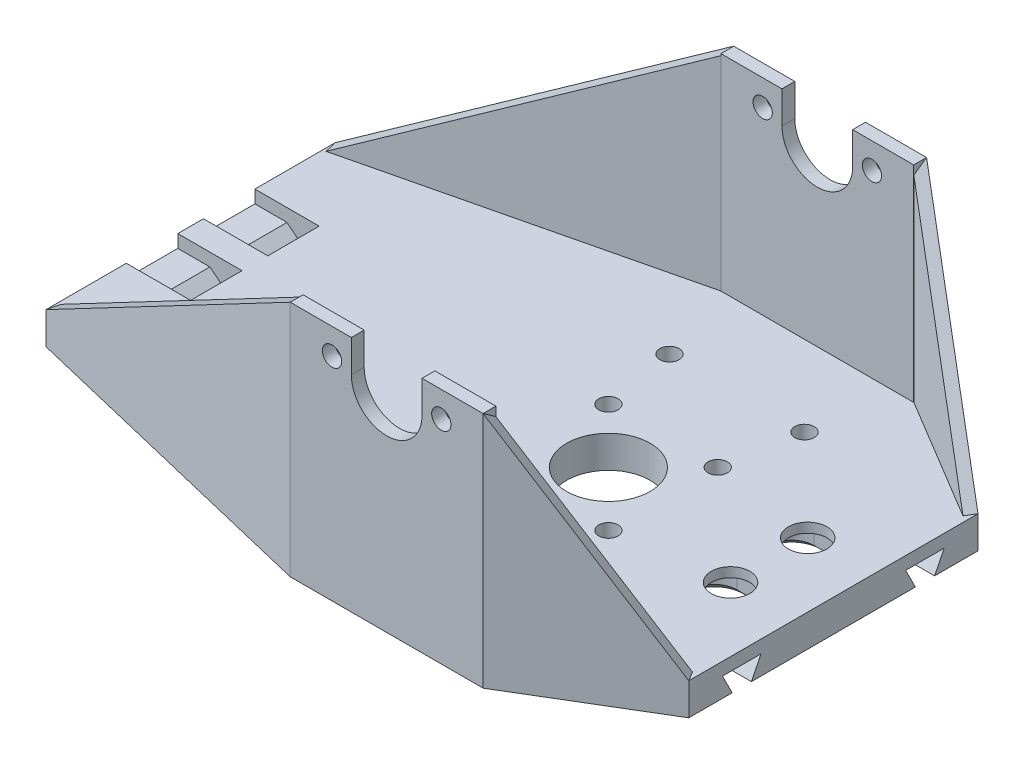
SolidWorks part; units mm, degrees
ref_plane "Front Plane" through (0, 0, 0) normal (0, 0, 1) x (1, 0, 0)
ref_plane "Top Plane" through (0, 0, 0) normal (0, 1, 0) x (1, 0, 0)
ref_plane "Right Plane" through (0, 0, 0) normal (1, 0, 0) x (0, 0, -1)
sketch "Sketch1" plane through (0, 0, 0) normal (0, 1, 0) x (1, 0, 0)
  line L1 (-15, 32.5) -> (15, 32.5)
  line L2 (-15, 32.5) -> (-15, -32.5)
  line L3 (-15, -32.5) -> (15, -32.5)
  line L4 (15, 32.5) -> (15, -32.5)
  point P4 (0, 32.5)
  point P6 (15, 0)
  dimension "D1" = 30
  dimension "D2" = 65
extrude "Boss-Extrude1" add sketch "Sketch1" along normal blind 2
sketch "Sketch5" plane through (0, 0, 32.5) normal (0, 0, 1) x (1, 0, 0)
  line L1 (-15, 0) -> (15, 0)
  line L2 (-15, 0) -> (-15, 34)
  line L3 (-15, 34) -> (15, 34)
  line L4 (15, 0) -> (15, 34)
  line L5 (-8.5, 0) -> (8.5, 0) construction
  line L6 (-8.5, 0) -> (-8.5, 30) construction
  line L7 (-8.5, 30) -> (8.5, 30) construction
  line L8 (8.5, 0) -> (8.5, 30) construction
  line L9 (-5.5, 34) -> (5.5, 34)
  line L10 (-5.5, 34) -> (-5.5, 29)
  line L11 (-5.5, 29) -> (5.5, 29) construction
  line L12 (5.5, 34) -> (5.5, 29)
  circle A0 centre (-8.5, 30) radius 1.5
  circle A1 centre (8.5, 30) radius 1.5
  arc A2 (-5.5, 29) -> (5.5, 29) centre (0, 29) ccw
  point P5 (0, 30)
  point P11 (0, 34)
  point P18 (0, 29)
  line M14 (-15, 0) -> (15, 0)
  line M15 (15, 0) -> (15, 2)
  line M16 (15, 2) -> (-15, 2)
  line M17 (-15, 2) -> (-15, 0)
  dimension "D4" = 3
  dimension "D5" = 3
  dimension "D1" = 34
  dimension "D2" = 30
  dimension "D3" = 17
  dimension "D6" = 11
  dimension "D7" = 5
extrude "Boss-Extrude2" add sketch "Sketch5" along normal blind 2 contours A2 L10 L3 L2 L4 L12 A1 A0 M16 | M17 M14 M15 M16 region at (0, 1, 32.5) region at (0, 16.4302, 32.5)
mirror "Mirror1" about plane through (0, 0, 0) normal (0, 0, 1) of "Boss-Extrude2"
sketch "Sketch6" plane through (0, 2, 0) normal (0, 1, 0) x (1, 0, 0)
  line L0 (15, -32.5) -> (15, 32.5) construction
  line L1 (-65, 22.5) -> (35, 22.5) construction
  line L2 (-65, 22.5) -> (-65, -22.5)
  line L3 (-65, -22.5) -> (35, -22.5) construction
  line L4 (35, 22.5) -> (35, -22.5)
  line L5 (-65, 22.5) -> (-15, 34.5)
  line L6 (-15, 34.5) -> (15, 34.5)
  line L7 (15, 34.5) -> (35, 22.5)
  line L8 (35, -22.5) -> (15, -34.5)
  line L9 (15, -34.5) -> (-15, -34.5)
  line L10 (-15, -34.5) -> (-65, -22.5)
  point P4 (35, 0)
  dimension "D1" = 45
  dimension "D2" = 100
  dimension "D3" = 20
extrude "Boss-Extrude3" add sketch "Sketch6" against normal blind 5
sketch "Sketch2" plane through (0, 2, 0) normal (0, 1, 0) x (1, 0, 0)
  circle A0 centre (0, 0) radius 6.5
  dimension "D1" = 13
extrude "Cut-Extrude1" cut sketch "Sketch2" against normal through all
sketch "Sketch3" plane through (0, 2, 0) normal (0, 1, 0) x (1, 0, 0)
  line L1 (8.5, 8.5) -> (-8.5, 8.5) construction
  line L2 (8.5, 8.5) -> (8.5, -8.5) construction
  line L3 (8.5, -8.5) -> (-8.5, -8.5) construction
  line L4 (-8.5, 8.5) -> (-8.5, -8.5) construction
  line L5 (8.5, 8.5) -> (-8.5, -8.5) construction
  line L6 (8.5, -8.5) -> (-8.5, 8.5) construction
  circle A0 centre (-8.5, 8.5) radius 1.5
  circle A1 centre (-8.5, -8.5) radius 1.5
  circle A2 centre (8.5, 8.5) radius 1.5
  circle A3 centre (8.5, -8.5) radius 1.5
  point P0 (0, 0)
  dimension "D3" = 3
  dimension "D4" = 3
  dimension "D5" = 3
  dimension "D6" = 3
  dimension "D1" = 17
  dimension "D2" = 17
extrude "Cut-Extrude2" cut sketch "Sketch3" against normal through all
sketch "Sketch4" plane through (0, 2, 0) normal (0, 1, 0) x (1, 0, 0)
  line L1 (10.5, -20) -> (-10.5, -20) construction
  line L2 (10.5, -20) -> (10.5, 20) construction
  line L3 (10.5, 20) -> (-10.5, 20) construction
  line L4 (-10.5, -20) -> (-10.5, 20) construction
  line L5 (10.5, -20) -> (-10.5, 20) construction
  line L6 (10.5, 20) -> (-10.5, -20) construction
  circle A0 centre (-10.5, 20) radius 1.5
  circle A1 centre (10.5, 20) radius 1.5
  circle A2 centre (10.5, -20) radius 1.5
  circle A3 centre (-10.5, -20) radius 1.5
  point P0 (0, 0)
  dimension "D3" = 3
  dimension "D4" = 3
  dimension "D5" = 3
  dimension "D6" = 3
  dimension "D1" = 21
  dimension "D2" = 40
extrude "Cut-Extrude3" cut sketch "Sketch4" against normal through all
sketch "Sketch8" plane through (19.1912, 0, -31.9853) normal (0.5145, 0, -0.8575) x (-0.8575, 0, -0.5145)
  line L0 (4.8877, 34) -> (-18.4361, 2)
  line L1 (-18.4361, 2) -> (4.8877, 2)
  line L2 (4.8877, 2) -> (4.8877, 34)
extrude "Boss-Extrude4" add sketch "Sketch8" against normal blind 1.7
mirror "Mirror2" about plane through (0, 0, 0) normal (0, 0, 1) of "Boss-Extrude4"
sketch "Sketch9" plane through (-8.646, 0, -36.025) normal (-0.2334, 0, -0.9724) x (-0.9724, 0, 0.2334)
  line L0 (57.9543, 2) -> (6.5344, 34)
  line L1 (6.5344, 34) -> (6.5344, 2)
  line L2 (6.5344, 2) -> (57.9543, 2)
extrude "Boss-Extrude5" add sketch "Sketch9" against normal blind 1.938
mirror "Mirror3" about plane through (0, 0, 0) normal (0, 0, 1) of "Boss-Extrude5"
sketch "Sketch10" plane through (0, -3, 0) normal (0, -1, 0) x (1, 0, 0)
  circle A0 centre (-10.5, 20) radius 2.75
  circle A1 centre (10.5, 20) radius 2.75
  circle A2 centre (8.5, 8.5) radius 2.75
  circle A3 centre (-8.5, 8.5) radius 2.75
  circle A4 centre (-8.5, -8.5) radius 2.75
  circle A5 centre (8.5, -8.5) radius 2.75
  circle A6 centre (10.5, -20) radius 2.75
  circle A7 centre (-10.5, -20) radius 2.75
  dimension "D1" = 5.5
  dimension "D2" = 5.5
  dimension "D3" = 5.5
  dimension "D4" = 5.5
  dimension "D5" = 5.5
  dimension "D6" = 5.5
  dimension "D7" = 5.5
  dimension "D8" = 5.5
extrude "Cut-Extrude4" cut sketch "Sketch10" against normal blind 2.5
sketch "Sketch11" plane through (-65, 0, 0) normal (-1, 0, 0) x (0, 0, 1)
  line L0 (-10, 0) -> (10, 0) construction
  line L2 (-22.5, 2) -> (22.5, 2) construction
  line L3 (-10, 0) -> (-2, 0)
  line L4 (-10, 0) -> (-10, 2)
  line L5 (-10, 2) -> (-2, 2)
  line L6 (-2, 0) -> (-2, 2)
  line L8 (10, 0) -> (2, 0)
  line L9 (10, 0) -> (10, 2)
  line L10 (10, 2) -> (2, 2)
  line L11 (2, 0) -> (2, 2)
  point P4 (0, 0)
  dimension "D1" = 20
  dimension "D2" = 8
  dimension "D3" = 8
extrude "Cut-Extrude5" cut sketch "Sketch11" against normal blind 10
sketch "Sketch12" plane through (0, 0, -2) normal (0, 0, -1) x (-1, 0, 0)
  line L0 (55, 0) -> (57.5, -2)
  line L1 (57.5, -2) -> (60, 0)
  line L2 (60, 0) -> (55, 0)
  line L4 (65, 2) -> (55, 2) construction
  line L5 (65, 2) -> (65, 0) construction
  line L6 (65, 0) -> (55, 0) construction
  line L7 (55, 2) -> (55, 0) construction
  point P0 (57.5, 0)
  point P2 (55, -0.0715)
  dimension "D1" = 5
  dimension "D2" = 2
  dimension "D3" = 10
  dimension "D4" = 2
extrude "Cut-Extrude6" cut sketch "Sketch12" along normal up to surface (-4 mm away) from surface up to face at (-60, 1, 2) starting at face at (-60, 1, 10)
extrude "Cut-Extrude7" cut sketch "Sketch12<2>" along normal up to surface (8 mm away) up to face at (-60, 1, -10)
sketch "Sketch12<2>" plane through (0, 0, -2) normal (0, 0, -1) x (-1, 0, 0) same geometry as "Sketch12"
sketch "Sketch13" plane through (0, -3, 0) normal (0, -1, 0) x (1, 0, 0)
  line L0 (-65, -22.5) -> (-65, 22.5) construction
  line L1 (-65, 15.75) -> (35, 15.75)
  line L2 (-65, 15.75) -> (-65, 12.75)
  line L3 (-65, 12.75) -> (35, 12.75)
  line L4 (35, 15.75) -> (35, 12.75)
  line L5 (35, 22.5) -> (35, -22.5) construction
  line L7 (-18.9194, 17.25) -> (20.7599, 17.25) construction
  line L8 (-18.9194, 17.25) -> (-18.9194, 11.25) construction
  line L9 (-18.9194, 11.25) -> (20.7599, 11.25) construction
  line L10 (20.7599, 17.25) -> (20.7599, 11.25) construction
  circle A0 centre (-10.5, 20) radius 2.75 construction
  circle A1 centre (-8.5, 8.5) radius 2.75 construction
  point P16 (-18.9194, 14.25)
  point P17 (-65, 14.25)
  dimension "D1" = 3
extrude "Cut-Extrude8" cut sketch "Sketch13" against normal blind 3
mirror "Mirror5" about plane through (0, 0, 0) normal (0, 0, 1) of "Cut-Extrude8"
sketch "Sketch14" plane through (-65, 0, 0) normal (-1, 0, 0) x (0, 0, 1)
  line L0 (12.75, -3) -> (11.25, 0)
  line L1 (11.25, 0) -> (12.75, 0)
  line L2 (12.75, 0) -> (15.75, 0)
  line L3 (15.75, 0) -> (17.25, 0)
  line L4 (17.25, 0) -> (15.75, -3)
  line L5 (15.75, -3) -> (12.75, -3)
  dimension "D1" = 1.5
  dimension "D2" = 1.5
extrude "Cut-Extrude9" cut sketch "Sketch14" against normal through all
mirror "Mirror6" about plane through (0, 0, 0) normal (0, 0, 1) of "Cut-Extrude9"
sketch "Sketch15" plane through (0, -3, 0) normal (0, -1, 0) x (1, 0, 0)
  line L0 (35, 12.75) -> (35, -12.75) construction
  circle A0 centre (25, -6) radius 3
  dimension "D1" = 6
  dimension "D2" = 10
  dimension "D3" = 6
extrude "Cut-Extrude10" cut sketch "Sketch15" against normal up to next
sketch "Sketch16" plane through (0, -3, 0) normal (0, -1, 0) x (1, 0, 0)
  line L0 (22.5, -6) -> (27.5, -6) construction
  line L1 (22.5, -2.5) -> (27.5, -2.5)
  line L2 (22.5, -9.5) -> (27.5, -9.5)
  arc A0 (22.5, -2.5) -> (22.5, -9.5) centre (22.5, -6) ccw
  arc A1 (27.5, -9.5) -> (27.5, -2.5) centre (27.5, -6) ccw
  circle A2 centre (25, -6) radius 3 construction
  point P2 (25, -6)
  point P7 (0, 0)
  dimension "D1" = 5
  dimension "D2" = 7
extrude "Cut-Extrude11" cut sketch "Sketch16" against normal blind 3.5
mirror "Mirror7" about plane through (0, 0, 0) normal (0, 0, 1) of "Cut-Extrude11", "Cut-Extrude10"
chamfer "Chamfer1" distance 1 angle 44 4 edges at (31, -3, 6) (25, -3, 9.5) (19, -3, 6) (25, -3, 2.5) first distance on face at (29.25, -1.25, 6) first distance on face at (25, -1.25, 9.5) first distance on face at (20.75, -1.25, 6) first distance on face at (25, -1.25, 2.5)
chamfer "Chamfer2" distance 1 angle 44 4 edges at (25, -3, -9.5) (31, -3, -6) (25, -3, -2.5) (19, -3, -6) first distance on face at (25, -3, 6)
equation "\"1.7.00mm\"=2"
